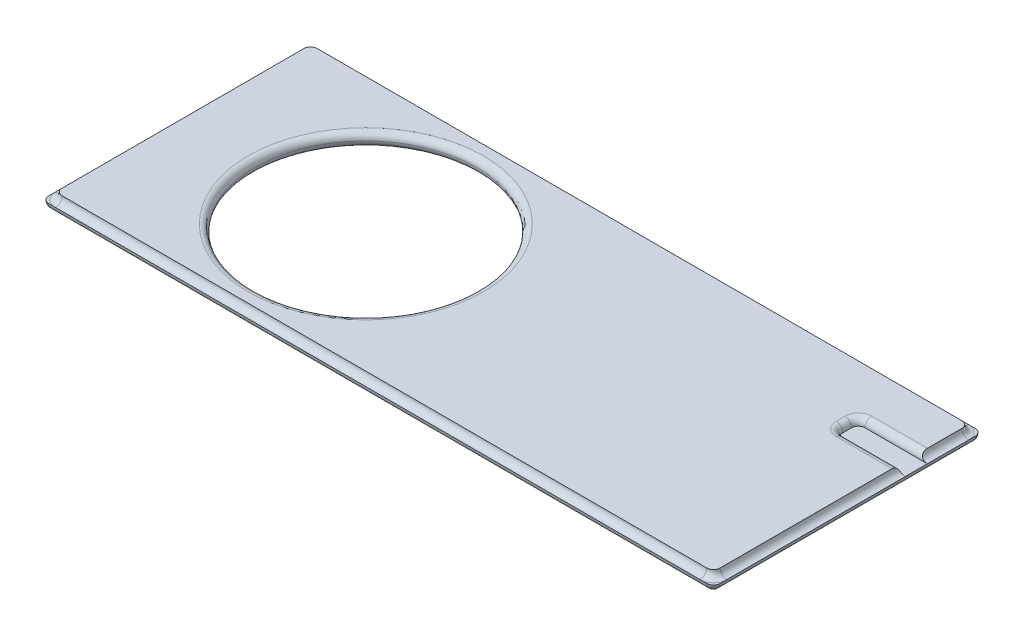
SolidWorks part; units mm, degrees
ref_plane "Front Plane" through (0, 0, 0) normal (0, 0, 1) x (1, 0, 0)
ref_plane "Top Plane" through (0, 0, 0) normal (0, 1, 0) x (1, 0, 0)
ref_plane "Right Plane" through (0, 0, 0) normal (1, 0, 0) x (0, 0, -1)
sketch "Sketch1" plane through (0, 0, 0) normal (0, 1, 0) x (1, 0, 0)
  line L1 (100, 40) -> (-100, 40)
  line L2 (100, 40) -> (100, -40)
  line L3 (100, -40) -> (-100, -40)
  line L4 (-100, 40) -> (-100, -40)
  line L5 (100, 40) -> (-100, -40) construction
  line L6 (100, -40) -> (-100, 40) construction
  point P0 (0, 0)
  dimension "D1" = 200
  dimension "D2" = 80
extrude "Boss-Extrude1" add sketch "Sketch1" along normal blind 2
sketch "Sketch2" plane through (0, 2, 0) normal (0, 1, 0) x (1, 0, 0)
  line L1 (98, 38) -> (-98, 38)
  line L2 (98, 38) -> (98, -38)
  line L3 (98, -38) -> (-98, -38)
  line L4 (-98, 38) -> (-98, -38)
  line L5 (98, 38) -> (-98, -38) construction
  line L6 (98, -38) -> (-98, 38) construction
  point P0 (0, 0)
  dimension "D1" = 196
  dimension "D2" = 76
extrude "Boss-Extrude2" add sketch "Sketch2" along normal blind 2
fillet "Fillet1" radius 2 4 edges at (-100, 1, -40) (100, 1, -40) (100, 1, 40) (-100, 1, 40)
fillet "Fillet2" radius 2 4 edges at (98, 3, -38) (98, 3, 38) (-98, 3, 38) (-98, 3, -38)
fillet "Fillet3" radius 2 16 edges at (-99.4142, 0, -39.4142) (0, 0, -40) (99.4142, 0, -39.4142) (100, 0, 0) (99.4142, 0, 39.4142) (0, 0, 40) (-99.4142, 0, 39.4142) (-97.4142, 2, 37.4142) (-98, 2, 0) (-97.4142, 2, -37.4142) (0, 2, -38) (97.4142, 2, -37.4142) (98, 2, 0) (97.4142, 2, 37.4142) (-100, 0, 0) (0, 2, 38)
sketch "Sketch3" plane through (0, 0, 0) normal (0, -1, 0) x (1, 0, 0)
  line L0 (-98, 0) -> (-43.56, 0) construction
  line L1 (-98, 38) -> (-98, -38) construction
  circle A0 centre (-43.56, 0) radius 33.0722
  dimension "D1" = 66.1443
extrude "Cut-Extrude1" cut sketch "Sketch3" against normal blind 25
fillet "Fillet4" radius 2 1 edges at (-43.56, 0, -33.0722)
fillet "Fillet5" radius 2 1 edges at (-43.56, 4, -33.0722)
sketch "Sketch4" plane through (0, 4, 0) normal (0, 1, 0) x (1, 0, 0)
  line L0 (98, -36) -> (98, 36) construction
  line L1 (98, 23.7409) -> (79.4188, 23.7409)
  line L2 (98, 23.7409) -> (98, 17.1609)
  line L3 (98, 17.1609) -> (79.4188, 17.1609)
  line L4 (79.4188, 23.7409) -> (79.4188, 17.1609)
  dimension "D1" = 6.58
  dimension "D2" = 18.5812
extrude "Cut-Extrude3" cut sketch "Sketch4" against normal blind 2
sketch "Sketch5" plane through (0, 2, 0) normal (0, 1, 0) x (1, 0, 0)
  line L1 (98, 23.7409) -> (101.7417, 23.7409)
  line L2 (98, 23.7409) -> (98, 17.1609)
  line L3 (98, 17.1609) -> (101.7417, 17.1609)
  line L4 (101.7417, 23.7409) -> (101.7417, 17.1609)
extrude "Cut-Extrude4" cut sketch "Sketch5" along normal blind 2
fillet "Fillet6" radius 2 2 edges at (79.4188, 3, -17.1609) (79.4188, 3, -23.7409)
fillet "Fillet7" radius 2 5 edges at (80.0046, 4, -17.7467) (80.0046, 4, -23.1551) (79.4188, 4, -20.4509) (89.7094, 4, -17.1609) (89.7094, 4, -23.7409)
sketch "Sketch6" plane through (0, 4, 0) normal (0, 1, 0) x (1, 0, 0)
  line L0 (97.4142, 37.4142) -> (97.4142, 23.7409)
  line L1 (100, 23.7409) -> (81.4188, 23.7409) construction
  arc A0 (98, 36) -> (96, 38) centre (96, 36) ccw construction
  dimension "D1" = 13.6733
